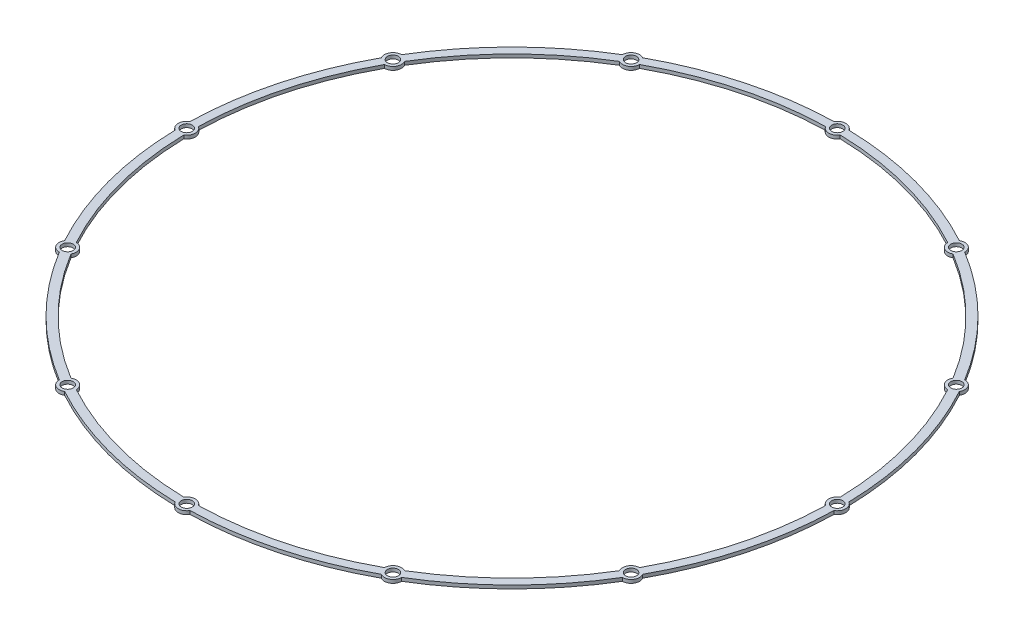
SolidWorks part; units mm, degrees
material "6061 Alloy"
ref_plane "Front Plane" through (0, 0, 0) normal (0, 0, 1) x (1, 0, 0)
ref_plane "Top Plane" through (0, 0, 0) normal (0, 1, 0) x (1, 0, 0)
ref_plane "Right Plane" through (0, 0, 0) normal (1, 0, 0) x (0, 0, -1)
sketch "Sketch1" plane through (0, 0, 0) normal (0, 1, 0) x (1, 0, 0)
  circle A0 centre (0, 0) radius 97.155 construction
  circle A1 centre (0, 0) radius 98.425
  circle A2 centre (0, 0) radius 95.885
  circle A3 centre (0, 0) radius 99.695
  circle A4 centre (0, 0) radius 94.615
  circle A5 centre (0, -97.155) radius 1.651
  circle A6 centre (0, -97.155) radius 2.54
  dimension "D1" = 194.31
  dimension "D6" = 3.302
  dimension "D2" = 1.27
  dimension "D3" = 1.27
  dimension "D4" = 2.54
  dimension "D5" = 2.54
extrude "Boss-Extrude1" add sketch "Sketch1" along normal blind 1.016 contours A6 A1 A2 | A2 A6 A1 A5 | A1 A5 A2 | A1 A6 A2 A5 region at (70.1763, 0, 68.6152) region at (-1.9395, 0, 97.1381) region at (1.9395, 0, 97.1381) region at (0, 0, 97.1536)
extrude "Boss-Extrude2" add sketch "Sketch1<3>" along normal blind 1.016 contours A2 A6 A5 | A6 A1 A5 region at (0, 0, 98.9993) region at (0, 0, 95.2997)
sketch "Sketch1<3>" plane through (0, 0, 0) normal (0, 1, 0) x (1, 0, 0) same geometry as "Sketch1"
extrude "Cut-Extrude1" cut sketch "Sketch1<4>" along normal up to surface (1.016 mm away) contours A1 A5 | A2 A5 | A1 A5 A2 region at (0, 0, 97.1536) region at (0, 0, 98.5779) region at (0, 0, 95.7299) up to face at (0, 1.016, 0.635)
sketch "Sketch1<4>" plane through (0, 0, 0) normal (0, 1, 0) x (1, 0, 0) same geometry as "Sketch1"
pattern_circular "CirPattern2" count 12 over 360 about axis through (0, 1.016, 0) along (0, 1, 0) of "Cut-Extrude1", "Boss-Extrude2"
ref_plane "Plane1" through (0, 0.508, 0) normal (0, 1, 0) x (1, 0, 0)
sketch "Sketch2" plane through (0, 0.508, 0) normal (0, 1, 0) x (1, 0, 0)
  circle A0 centre (-84.1387, 48.5775) radius 1.651 construction
  circle A1 centre (-48.5775, 84.1387) radius 1.651 construction
  circle A2 centre (-97.155, 0) radius 1.651 construction
  circle A3 centre (-84.1387, -48.5775) radius 1.651 construction
  circle A4 centre (-48.5775, -84.1387) radius 1.651 construction
  circle A5 centre (0, -97.155) radius 1.651 construction
  circle A6 centre (48.5775, -84.1387) radius 1.651 construction
  circle A7 centre (84.1387, -48.5775) radius 1.651 construction
  circle A8 centre (97.155, 0) radius 1.651 construction
  circle A9 centre (84.1387, 48.5775) radius 1.651 construction
  circle A10 centre (48.5775, 84.1387) radius 1.651 construction
  circle A11 centre (0, 97.155) radius 1.651 construction
  circle A12 centre (-84.1387, 48.5775) radius 1.651
  circle A13 centre (-97.155, 0) radius 1.651
  circle A14 centre (-84.1387, -48.5775) radius 1.651
  circle A15 centre (-48.5775, -84.1387) radius 1.651
  circle A16 centre (0, -97.155) radius 1.651
  circle A17 centre (48.5775, -84.1387) radius 1.651
  circle A18 centre (84.1387, -48.5775) radius 1.651
  circle A19 centre (97.155, 0) radius 1.651
  circle A20 centre (84.1387, 48.5775) radius 1.651
  circle A21 centre (48.5775, 84.1387) radius 1.651
  circle A22 centre (0, 97.155) radius 1.651
  circle A23 centre (-48.5775, 84.1387) radius 1.651
  arc A24 (-51.1173, -84.11) -> (-47.2828, -86.3239) centre (-48.5775, -84.1387) ccw
  arc A25 (-47.2828, -86.3239) -> (-2.2139, -98.4001) centre (0, 0) ccw
  arc A26 (-2.2139, -98.4001) -> (2.2139, -98.4001) centre (0, -97.155) ccw
  arc A27 (2.2139, -98.4001) -> (47.2828, -86.3239) centre (0, 0) ccw
  arc A28 (47.2828, -86.3239) -> (51.1173, -84.11) centre (48.5775, -84.1387) ccw
  arc A29 (51.1173, -84.11) -> (84.11, -51.1173) centre (0, 0) ccw
  arc A30 (84.11, -51.1173) -> (86.3239, -47.2828) centre (84.1387, -48.5775) ccw
  arc A31 (86.3239, -47.2828) -> (98.4001, -2.2139) centre (0, 0) ccw
  arc A32 (98.4001, -2.2139) -> (98.4001, 2.2139) centre (97.155, 0) ccw
  arc A33 (98.4001, 2.2139) -> (86.3239, 47.2828) centre (0, 0) ccw
  arc A34 (86.3239, 47.2828) -> (84.11, 51.1173) centre (84.1387, 48.5775) ccw
  arc A35 (84.11, 51.1173) -> (51.1173, 84.11) centre (0, 0) ccw
  arc A36 (51.1173, 84.11) -> (47.2828, 86.3239) centre (48.5775, 84.1387) ccw
  arc A37 (47.2828, 86.3239) -> (2.2139, 98.4001) centre (0, 0) ccw
  arc A38 (2.2139, 98.4001) -> (-2.2139, 98.4001) centre (0, 97.155) ccw
  arc A39 (-2.2139, 98.4001) -> (-47.2828, 86.3239) centre (0, 0) ccw
  arc A40 (-47.2828, 86.3239) -> (-51.1173, 84.11) centre (-48.5775, 84.1387) ccw
  arc A41 (-51.1173, 84.11) -> (-84.11, 51.1173) centre (0, 0) ccw
  arc A42 (-84.11, 51.1173) -> (-86.3239, 47.2828) centre (-84.1387, 48.5775) ccw
  arc A43 (-86.3239, 47.2828) -> (-98.4001, 2.2139) centre (0, 0) ccw
  arc A44 (-98.4001, 2.2139) -> (-98.4001, -2.2139) centre (-97.155, 0) ccw
  arc A45 (-98.4001, -2.2139) -> (-86.3239, -47.2828) centre (0, 0) ccw
  arc A46 (-86.3239, -47.2828) -> (-84.11, -51.1173) centre (-84.1387, -48.5775) ccw
  arc A47 (-84.11, -51.1173) -> (-51.1173, -84.11) centre (0, 0) ccw
  arc A48 (-51.1173, -84.11) -> (-47.2828, -86.3239) centre (-48.5775, -84.1387) ccw
  arc A49 (-47.2828, -86.3239) -> (-2.2139, -98.4001) centre (0, 0) ccw
  arc A50 (-2.2139, -98.4001) -> (2.2139, -98.4001) centre (0, -97.155) ccw
  arc A51 (2.2139, -98.4001) -> (47.2828, -86.3239) centre (0, 0) ccw
  arc A52 (47.2828, -86.3239) -> (51.1173, -84.11) centre (48.5775, -84.1387) ccw
  arc A53 (51.1173, -84.11) -> (84.11, -51.1173) centre (0, 0) ccw
  arc A54 (84.11, -51.1173) -> (86.3239, -47.2828) centre (84.1387, -48.5775) ccw
  arc A55 (86.3239, -47.2828) -> (98.4001, -2.2139) centre (0, 0) ccw
  arc A56 (98.4001, -2.2139) -> (98.4001, 2.2139) centre (97.155, 0) ccw
  arc A57 (98.4001, 2.2139) -> (86.3239, 47.2828) centre (0, 0) ccw
  arc A58 (86.3239, 47.2828) -> (84.11, 51.1173) centre (84.1387, 48.5775) ccw
  arc A59 (84.11, 51.1173) -> (51.1173, 84.11) centre (0, 0) ccw
  arc A60 (51.1173, 84.11) -> (47.2828, 86.3239) centre (48.5775, 84.1387) ccw
  arc A61 (47.2828, 86.3239) -> (2.2139, 98.4001) centre (0, 0) ccw
  arc A62 (2.2139, 98.4001) -> (-2.2139, 98.4001) centre (0, 97.155) ccw
  arc A63 (-2.2139, 98.4001) -> (-47.2828, 86.3239) centre (0, 0) ccw
  arc A64 (-47.2828, 86.3239) -> (-51.1173, 84.11) centre (-48.5775, 84.1387) ccw
  arc A65 (-51.1173, 84.11) -> (-84.11, 51.1173) centre (0, 0) ccw
  arc A66 (-84.11, 51.1173) -> (-86.3239, 47.2828) centre (-84.1387, 48.5775) ccw
  arc A67 (-86.3239, 47.2828) -> (-98.4001, 2.2139) centre (0, 0) ccw
  arc A68 (-98.4001, 2.2139) -> (-98.4001, -2.2139) centre (-97.155, 0) ccw
  arc A69 (-98.4001, -2.2139) -> (-86.3239, -47.2828) centre (0, 0) ccw
  arc A70 (-86.3239, -47.2828) -> (-84.11, -51.1173) centre (-84.1387, -48.5775) ccw
  arc A71 (-84.11, -51.1173) -> (-51.1173, -84.11) centre (0, 0) ccw
  dimension "D1" = 0
equation "\"Middle Coupler Inner Daimeter\"= 6.75in"
equation "\"Middle Coupler  Wall Thickness\" = 0.25in"
equation "\"Middle Coupler Bottom Thickness\"= 0.2in"
equation "\"Bearing Rail Offset\"= 0.45in"
equation "\"3-56 UNF Tap\"= 0.089in"
equation "\"3-56 UNF Clearance\"= 0.104in"
equation "\"Ball Bearing Distance\"= 0.03in"
equation "\"TCA Outer Diameter\" = 8.625in"
equation "\"D1@Sketch1\"=\"Middle Coupler Inner Daimeter\"+\"Bearing Rail Offset\"*2in"
